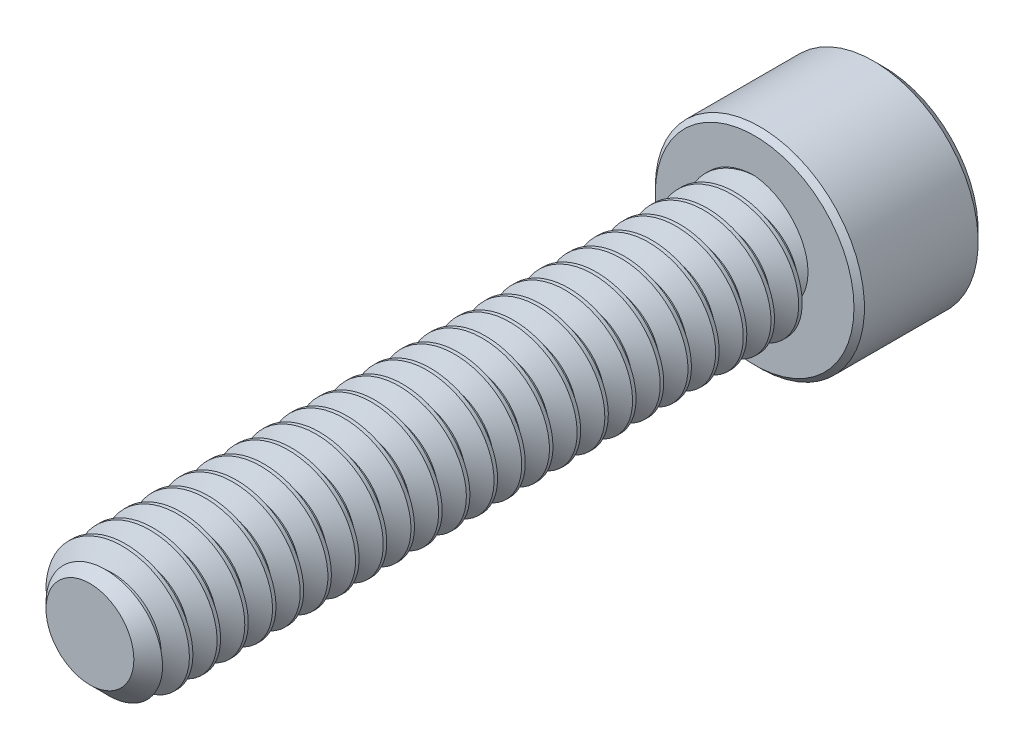
SolidWorks part; units mm, degrees
ref_plane "Front Plane" through (0, 0, 0) normal (0, 0, 1) x (1, 0, 0)
ref_plane "Top Plane" through (0, 0, 0) normal (0, 1, 0) x (1, 0, 0)
ref_plane "Right Plane" through (0, 0, 0) normal (1, 0, 0) x (0, 0, -1)
sketch "Sketch0" plane through (0, 0, 0) normal (1, 0, 0) x (0, 0, -1)
  line L0 (0, 0) -> (9.525, 0) construction
  point P2 (11.3792, 0)
  point P4 (0.254, 0)
  dimension "D1" = 9.525
  dimension "D2" = 1.8542
  dimension "Min Thread" = 0.254
sketch "Sketch1" plane through (0, 0, 0) normal (0, 0, 1) x (1, 0, 0)
  circle A0 centre (0, 0) radius 0.9271
  dimension "OD" = 1.8542
extrude "Extrude1" add sketch "Sketch1" against normal blind 9.525
sketch "Sketch2" plane through (0, 0, 0) normal (0, 0, 1) x (1, 0, 0)
  circle A0 centre (0, 0) radius 0.9271 construction
  circle A1 centre (0, 0) radius 0.9271
curve "Helix/Spiral1" pitch 0.3969 height 9.9219 turns 25 parameters "pitch"=0.3969
chamfer "Chamfer3" distance 0.2977 angle 45 1 edges at (0.9271, 0, 0)
sketch "Sketch3" plane through (0, 0, 0) normal (1, 0, 0) x (0, 0, -1)
  line L0 (-0.3473, 0.9271) -> (-0.1984, 0.6693)
  line L1 (-0.1984, 0.6693) -> (-0.1488, 0.6693)
  line L2 (-0.1488, 0.6693) -> (0, 0.9271)
  line L3 (-0.3473, 0.9271) -> (0, 0.9271)
  line L4 (-0.1736, 0.9271) -> (-0.1736, 0.6693) construction
  line L5 (-0.2729, 0.7982) -> (-0.0744, 0.7982) construction
  line L6 (0, 0.9271) -> (0, -0.9271) construction
  dimension "D1" = 0.0496
  dimension "D2" = 0.1984
  dimension "D3" = 60
sweep "Cut-Sweep1" cut profiles "Sketch3" path "Helix/Spiral1"
sketch "Sketch5" plane through (0, 0, 0) normal (1, 0, 0) x (0, 0, -1)
  line L0 (9.525, -0.6771) -> (9.525, 0.6615) construction
  line L1 (9.525, 0.9271) -> (0.254, 0.9271)
  line L2 (9.525, 0.9271) -> (9.525, 0)
  line L3 (9.525, 0) -> (-0.0834, 0)
  line L4 (0, 0) -> (9.525, 0) construction
  line L5 (0.254, 0.9271) -> (-0.0834, 0)
  line L6 (0, 0) -> (12.065, 0) construction
  dimension "D1" = 70
  dimension "D3" = 2.54
revolve "partially thread" [suppressed] add sketch "Sketch5" angle 360 about L6
sketch "Sketch6" plane through (0, 0, -9.525) normal (0, 0, -1) x (-1, 0, 0)
  circle A0 centre (0, 0) radius 1.4986
  dimension "head dia" = 2.9972
extrude "Extrude2" add sketch "Sketch6" along normal blind 1.8542
sketch "Sketch7" plane through (0, 0, -11.3792) normal (0, 0, -1) x (-1, 0, 0)
  line L1 (0, 0.9165) -> (-0.7937, 0.4583)
  line L2 (-0.7937, 0.4583) -> (-0.7937, -0.4583)
  line L3 (-0.7937, -0.4583) -> (0, -0.9165)
  line L4 (0, -0.9165) -> (0.7938, -0.4583)
  line L5 (0.7938, -0.4583) -> (0.7938, 0.4583)
  line L6 (0.7938, 0.4583) -> (0, 0.9165)
  circle A0 centre (0, 0) radius 0.7937 construction
  dimension "hex dia" = 1.5875
extrude "Cut-Extrude1" cut sketch "Sketch7" against normal blind 1.1906
sketch "Sketch8" plane through (0, 0, -11.3792) normal (0, 0, -1) x (-1, 0, 0)
  circle A0 centre (0, 0) radius 0.9165
extrude "Cut-Extrude2" cut sketch "Sketch8" against normal through all draft 45
chamfer "Chamfer1" distance 0.1499 angle 45 1 edges at (-1.4986, 0, -11.3792)
chamfer "Chamfer2" distance 0.0749 angle 45 1 edges at (-1.4986, 0, -9.525)
sketch "Sketch9" plane through (0, 0, 0) normal (1, 0, 0) x (0, 0, -1)
  line L0 (0, 0.9271) -> (0, -0.9271) construction
  line L1 (1.7859, 0.9271) -> (1.7859, -0.9271) construction
  line L2 (11.3792, 1.4986) -> (11.3792, -1.4986) construction
  line L3 (9.525, 1.4986) -> (9.525, -1.4986) construction
  line L4 (9.525, 1.4237) -> (9.525, -1.4237) construction
  line L5 (11.3792, -1.3487) -> (11.3792, 1.3487) construction
  line L6 (9.525, -1.4986) -> (9.525, 1.4986) construction
  line L7 (0, 0.6294) -> (0, -0.6294) construction
  line L8 (-0.3473, 0.9271) -> (0, 0.9271) construction
  line L9 (1.7859, 0) -> (0, 0) construction
  dimension "D1" = 1.7859
equation "\"D3@Helix/Spiral1\" = \"screw length@Extrude1\"+\"pitch@Helix/Spiral1\""
equation "\"D1@Sketch3\" = \"pitch@Helix/Spiral1\"*.125"
equation "\"D2@Sketch3\" = \"pitch@Helix/Spiral1\"*.5"
equation "\"D1@Cut-Extrude1\" = \"hex dia@Sketch7\"*.75"
equation "\"D1@Chamfer1\" = \"head dia@Sketch6\"*.05"
equation "\"D1@Sketch9\" = \"pitch@Helix/Spiral1\"*4.50"
equation "\"D1@Chamfer2\" = \"D1@Chamfer1\"/2"
equation "\"D1@Chamfer3\" = \"pitch@Helix/Spiral1\"*.750"
equation "\"D1@Sketch0\" = \"screw length@Extrude1\""
equation "\"D2@Sketch0\" = \"head depth@Extrude2\""
